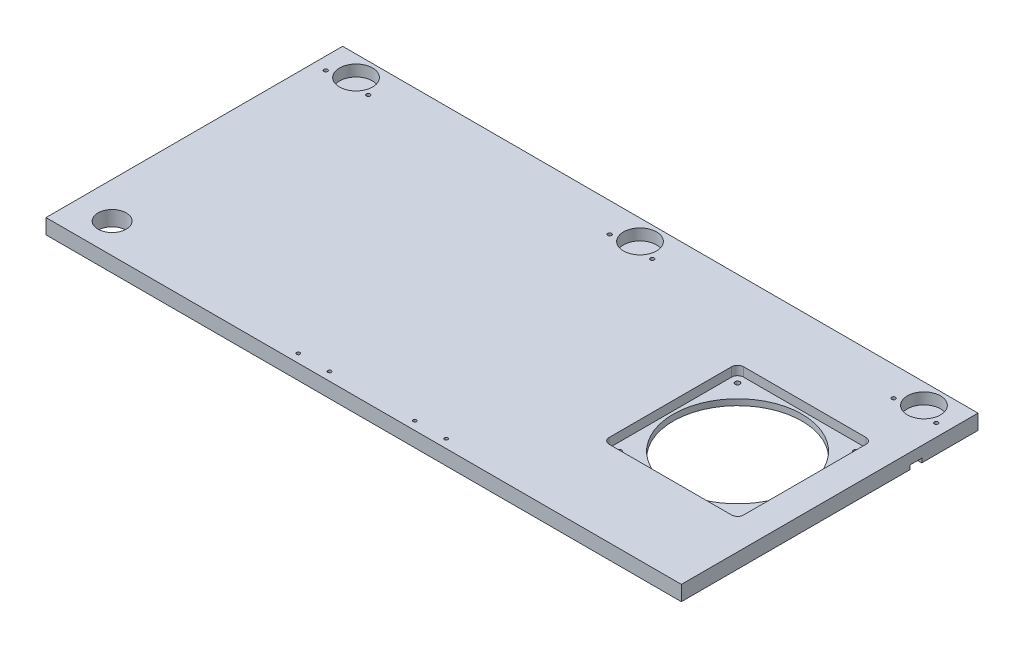
SolidWorks part; units mm, degrees
ref_plane "Front Plane" through (0, 0, 0) normal (0, 0, 1) x (1, 0, 0)
ref_plane "Top Plane" through (0, 0, 0) normal (0, 1, 0) x (1, 0, 0)
ref_plane "Right Plane" through (0, 0, 0) normal (1, 0, 0) x (0, 0, -1)
sketch "Sketch1" plane through (0, 0, 0) normal (0, 1, 0) x (1, 0, 0)
  line L1 (335.6356, 156.7053) -> (-335.6356, 156.7053)
  line L2 (335.6356, 156.7053) -> (335.6356, -156.7053)
  line L3 (335.6356, -156.7053) -> (-335.6356, -156.7053)
  line L4 (-335.6356, 156.7053) -> (-335.6356, -156.7053)
  line L5 (335.6356, 156.7053) -> (-335.6356, -156.7053) construction
  line L6 (335.6356, -156.7053) -> (-335.6356, 156.7053) construction
  point P0 (0, 0)
  dimension "D1" = 671.2712
  dimension "D2" = 313.4106
extrude "Boss-Extrude1" add sketch "Sketch1" along normal blind 15.875
sketch "Sketch2" plane through (0, 15.875, 0) normal (0, 1, 0) x (1, 0, 0)
  line L0 (335.6356, 156.7053) -> (-335.6356, 156.7053) construction
  line L1 (343.5731, 137.6553) -> (-343.5731, 137.6553)
  line L2 (343.5731, 137.6553) -> (343.5731, -137.6553)
  line L3 (343.5731, -137.6553) -> (-343.5731, -137.6553)
  line L4 (-343.5731, 137.6553) -> (-343.5731, -137.6553)
  line L5 (343.5731, 137.6553) -> (-343.5731, -137.6553) construction
  line L6 (343.5731, -137.6553) -> (-343.5731, 137.6553) construction
  line L7 (-335.6356, 156.7053) -> (-335.6356, -156.7053) construction
  point P0 (0, 0)
  dimension "D1" = 19.05
  dimension "D2" = 7.9375
extrude "Boss-Extrude2" [suppressed] add sketch "Sketch2" against normal up to surface (15.875 mm away) up to face at (0, 0, 0)
fillet "Fillet1" [suppressed] radius 6.35
sketch "Sketch4" plane through (0, 15.875, 0) normal (0, 1, 0) x (1, 0, 0)
  line L1 (0, 0) -> (0, -124.9553) construction
  line L2 (-335.6356, -156.7053) -> (335.6356, -156.7053) construction
  line L3 (-335.6356, 156.7053) -> (-335.6356, -156.7053) construction
  circle A1 centre (-297.5356, -124.9553) radius 14.9225
  dimension "D3" = 31.75
  dimension "D5" = 29.845
  dimension "D4" = 38.1
extrude "Cut-Extrude2" cut sketch "Sketch4" against normal through all both and the other way through all
sketch "Sketch5" plane through (0, 15.875, 0) normal (0, 1, 0) x (1, 0, 0)
  line L0 (0, 0) -> (0, 156.7053) construction
  line L1 (335.6356, 156.7053) -> (-335.6356, 156.7053) construction
  line L2 (-300, 135.2428) -> (-300, 146.2735) construction
  circle A0 centre (0, 135.2428) radius 17.4625
  circle A1 centre (22.5, 125.7428) radius 2
  circle A2 centre (-22.5, 125.7428) radius 2
  circle A3 centre (-300, 135.2428) radius 17.4625
  circle A4 centre (-277.5, 125.7428) radius 2
  circle A5 centre (-322.5, 125.7428) radius 2
  circle A6 centre (322.5, 125.7428) radius 2
  circle A7 centre (277.5, 125.7428) radius 2
  circle A8 centre (300, 135.2428) radius 17.4625
  dimension "D1" = 34.925
  dimension "D3" = 45
  dimension "D4" = 4
  dimension "D6" = 4
  dimension "D5" = 9.5
  dimension "D2" = 45
  dimension "D7" = 300
extrude "Cut-Extrude3" cut sketch "Sketch5" against normal blind 11.9062
sketch "Sketch6" plane through (0, 15.875, 0) normal (0, 1, 0) x (1, 0, 0)
  line L0 (-335.6356, -156.7053) -> (335.6356, -156.7053) construction
  line L1 (78.05, -147.7053) -> (45.05, -147.7053) construction
  line L2 (-45.05, -147.7053) -> (-78.05, -147.7053) construction
  circle A0 centre (78.05, -147.7053) radius 1.8
  circle A1 centre (45.05, -147.7053) radius 1.8
  circle A2 centre (-45.05, -147.7053) radius 1.8
  circle A4 centre (-78.05, -147.7053) radius 1.8
  point P8 (61.55, -147.7053)
  point P12 (-61.55, -147.7053)
  dimension "D2" = 3.6
  dimension "D3" = 33
  dimension "D1" = 9
  dimension "D4" = 33
  dimension "D5" = 61.55
  dimension "D6" = 61.55
extrude "Cut-Extrude4" cut sketch "Sketch6" against normal blind 2.54
sketch "Sketch7" plane through (0, 15.875, 0) normal (0, 1, 0) x (1, 0, 0)
  line L2 (335.6356, 156.7053) -> (-335.6356, 156.7053) construction
  line L3 (335.6356, -156.7053) -> (335.6356, 156.7053) construction
  circle A0 centre (234.0356, 4.3053) radius 68
  circle A1 centre (296.5356, -58.1947) radius 2.54
  circle A2 centre (296.5356, 66.8053) radius 2.54
  circle A3 centre (171.5356, 66.8053) radius 2.54
  circle A4 centre (171.5356, -58.1947) radius 2.54
  circle A5 centre (234.0356, 4.3053) radius 88.3883 construction
  dimension "D1" = 125
  dimension "D2" = 125
  dimension "D3" = 5.08
  dimension "D4" = 136
  dimension "D5" = 152.4
  dimension "D6" = 101.6
extrude "Cut-Extrude5" cut sketch "Sketch7" against normal through all both and the other way through all
sketch "Sketch8" plane through (0, 15.875, 0) normal (0, 1, 0) x (1, 0, 0)
  line L1 (169.3856, -66.6947) -> (298.6856, -66.6947)
  line L2 (163.0356, -60.3447) -> (163.0356, 68.9553)
  line L3 (169.3856, 75.3053) -> (298.6856, 75.3053)
  line L4 (305.0356, -60.3447) -> (305.0356, 68.9553)
  line L5 (163.0356, -66.6947) -> (305.0356, 75.3053) construction
  line L6 (163.0356, 75.3053) -> (305.0356, -66.6947) construction
  arc A0 (163.0356, 68.9553) -> (169.3856, 75.3053) centre (169.3856, 68.9553) cw
  arc A1 (298.6856, 75.3053) -> (305.0356, 68.9553) centre (298.6856, 68.9553) cw
  arc A2 (298.6856, -66.6947) -> (305.0356, -60.3447) centre (298.6856, -60.3447) ccw
  arc A3 (169.3856, -66.6947) -> (163.0356, -60.3447) centre (169.3856, -60.3447) cw
  point P0 (234.0356, 4.3053)
  dimension "D3" = 6.35
  dimension "D1" = 142
  dimension "D2" = 142
extrude "Cut-Extrude6" cut sketch "Sketch8" against normal blind 9.525
sketch "Sketch9" plane through (0, 0, 0) normal (0, -1, 0) x (1, 0, 0)
  line L0 (335.6356, 156.7053) -> (335.6356, -156.7053) construction
  line L1 (335.6356, -97.2947) -> (-335.6356, -97.2947)
  line L2 (335.6356, -97.2947) -> (335.6356, -84.7947)
  line L3 (335.6356, -84.7947) -> (-335.6356, -84.7947)
  line L4 (-335.6356, -97.2947) -> (-335.6356, -84.7947)
  line L5 (-335.6356, -156.7053) -> (-335.6356, 156.7053) construction
  line L6 (-335.6356, 156.7053) -> (335.6356, 156.7053) construction
  dimension "D1" = 12.5
  dimension "D2" = 254
extrude "Cut-Extrude7" cut sketch "Sketch9" against normal blind 4.35
